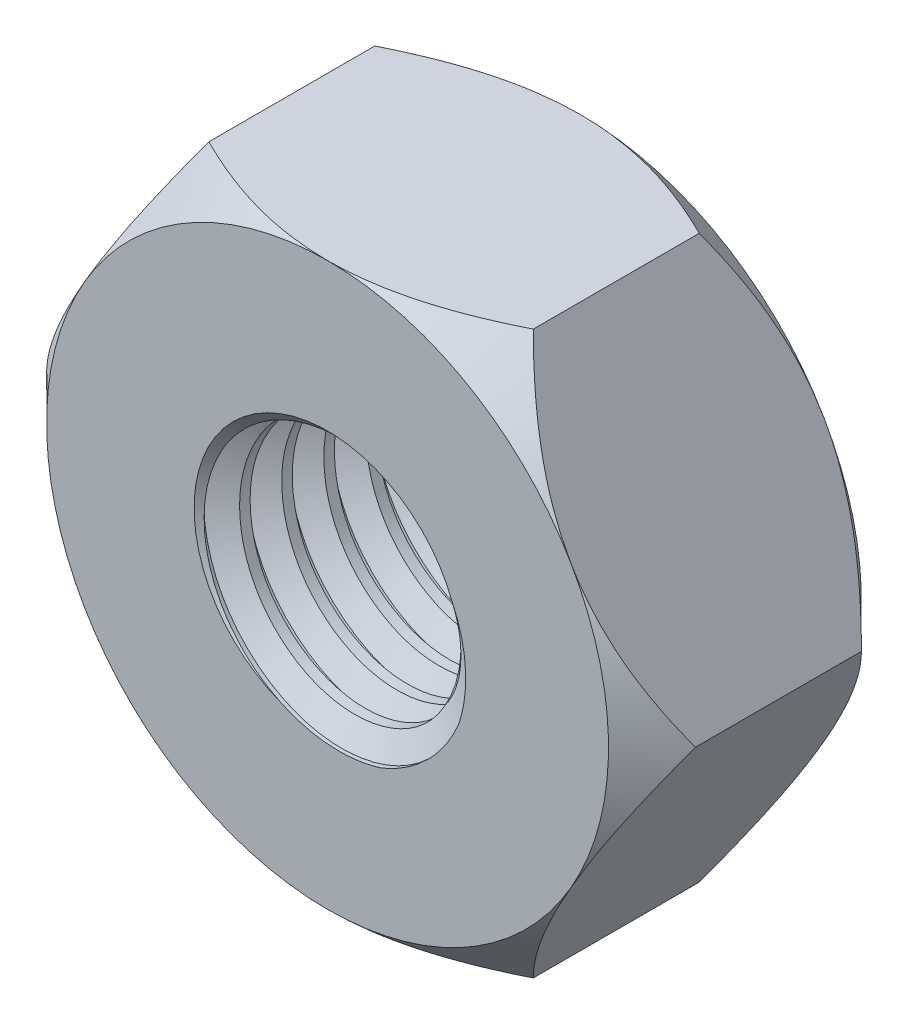
SolidWorks part; units mm, degrees
ref_plane "Front Plane" through (0, 0, 0) normal (0, 0, 1) x (1, 0, 0)
ref_plane "Top Plane" through (0, 0, 0) normal (0, 1, 0) x (1, 0, 0)
ref_plane "Right Plane" through (0, 0, 0) normal (1, 0, 0) x (0, 0, -1)
sketch "Sketch1" plane through (0, 0, 0) normal (0, 0, 1) x (1, 0, 0)
  line L1 (11.547, 0) -> (5.7735, 10)
  line L2 (5.7735, 10) -> (-5.7735, 10)
  line L3 (-5.7735, 10) -> (-11.547, 0)
  line L4 (-11.547, 0) -> (-5.7735, -10)
  line L5 (-5.7735, -10) -> (5.7735, -10)
  line L6 (5.7735, -10) -> (11.547, 0)
  circle A0 centre (0, 0) radius 10 construction
  dimension "D1" = 20
extrude "Boss-Extrude1" add sketch "Sketch1" along normal mid plane 9
sketch "Sketch2" plane through (0, 0, 4.5) normal (0, 0, 1) x (1, 0, 0)
  line L0 (-5.7735, 10) -> (-11.547, 0) construction
  circle A0 centre (0, 0) radius 10
extrude "Cut-Extrude1" cut sketch "Sketch2" against normal through all draft 45 flip side to cut
mirror "Mirror1" about plane through (0, 0, 0) normal (0, 0, 1) of "Cut-Extrude1"
sketch "Sketch3" plane through (0, 0, 4.5) normal (0, 0, 1) x (1, 0, 0)
  circle A0 centre (0, 0) radius 4.25
  dimension "D1" = 8.5
extrude "Cut-Extrude2" cut sketch "Sketch3" against normal through all
chamfer "Chamfer1" distance 0.5 angle 45 2 edges at (4.25, 0, -4.5) (4.25, 0, 4.5)
thread "Thread1" pitch 1.5 method cut profile "Thread Profile3" start angle 0, offset 2, length 0, pitch 1.5, diameter 8.5
ref_plane "Plane3" through (-4.25, 0, 6) normal (0, -1, 0) x (-1, 0, 0)
sketch "Thread Profile3" plane through (-4.25, 0, 6) normal (0, -1, 0) x (-1, 0, 0)
  line L0 (0, 0) -> (0, 1.5) construction
  line L1 (0, 0) -> (0.8119, 0.4687)
  line L2 (0.8119, 0.4687) -> (0.8119, 0.6562)
  line L3 (0.8119, 0.6562) -> (0, 1.125)
  line L4 (0.8119, 0.5625) -> (0, 0.5625) construction
  line L11 (0, 0) -> (0, 1.125)
  point P2 (0, 0)
  dimension "Pitch" = 1.5
  dimension "Profile_Angle" = 60
  dimension "Profile_Land" = 0.1875
  dimension "Profile_Height" = 0.8119
